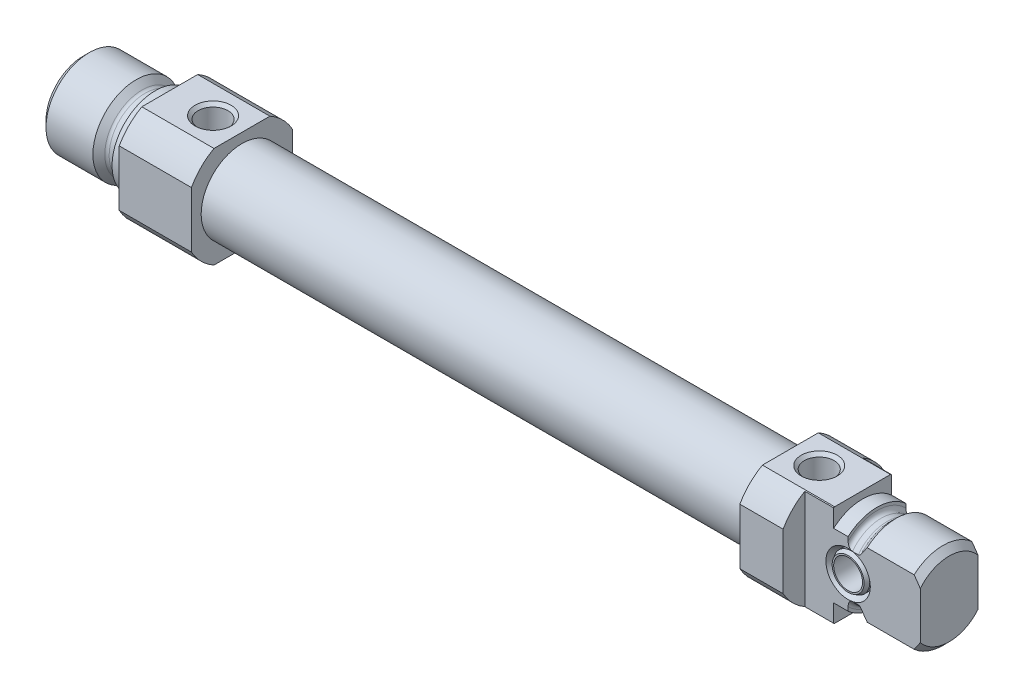
SolidWorks part; units mm, degrees
ref_plane "Front Plane" through (0, 0, 0) normal (0, 0, 1) x (1, 0, 0)
ref_plane "Top Plane" through (0, 0, 0) normal (0, 1, 0) x (1, 0, 0)
ref_plane "Right Plane" through (0, 0, 0) normal (1, 0, 0) x (0, 0, -1)
sketch "Sketch1" plane through (0, 0, 0) normal (0, 0, 1) x (1, 0, 0)
  line L0 (0, 0) -> (0, 5.15)
  line L1 (0, 5.15) -> (0.85, 6)
  line L2 (0.85, 6) -> (7.35, 6)
  line L3 (7.35, 6) -> (8.1743, 5.1757)
  line L4 (8.5985, 5) -> (9.4, 5)
  line L5 (10, 5.6) -> (10, 6)
  line L6 (10, 6) -> (12, 6)
  line L7 (12, 6) -> (12, 0)
  line L8 (12, 0) -> (0, 0)
  line L9 (12, 0) -> (0, 0) construction
  arc A0 (8.1743, 5.1757) -> (8.5985, 5) centre (8.5985, 5.6) ccw
  arc A1 (9.4, 5) -> (10, 5.6) centre (9.4, 5.6) ccw
revolve "Revolve1" add sketch "Sketch1" angle 360 about L9 reverse direction yes
cosmetic thread "Cosmetic Thread1" parameters "D1"=7.267, "D2"=10.466
ref_plane "Plane1" through (3, 0, 0) normal (1, 0, 0) x (0, 0, -1)
ref_plane "Plane2" through (8, 0, 0) normal (1, 0, 0) x (0, 0, -1)
ref_plane "Plane3" through (0, -8, 0) normal (0, 1, 0) x (1, 0, 0)
ref_plane "Plane4" through (0, 0, 0) normal (0, 1, 0) x (1, 0, 0)
ref_plane "Plane5" through (0, 0, 0) normal (0, 1, 0) x (1, 0, 0)
ref_plane "Plane6" through (0, 0, 0) normal (0, 1, 0) x (1, 0, 0)
ref_plane "Plane7" through (12, 0, 0) normal (1, 0, 0) x (0, 0, -1)
ref_plane "Plane8" through (12, 0, 0) normal (1, 0, 0) x (0, 0, -1)
ref_plane "Plane9" through (20, 0, 0) normal (1, 0, 0) x (0, 0, -1)
ref_plane "Plane10" through (12, 0, 0) normal (1, 0, 0) x (0, 0, -1)
ref_plane "Plane11" through (12, 0, 0) normal (1, 0, 0) x (0, 0, -1)
sketch "Sketch2" plane through (12, 0, 0) normal (1, 0, 0) x (0, 0, -1)
  line L0 (-3.873, -7) -> (3.873, -7)
  line L1 (7, -3.873) -> (7, 3.873)
  line L2 (3.873, 7) -> (-3.873, 7)
  line L3 (-7, 3.873) -> (-7, -3.873)
  arc A0 (-7, -3.873) -> (-3.873, -7) centre (0, 0) ccw
  arc A1 (3.873, -7) -> (7, -3.873) centre (0, 0) ccw
  arc A2 (7, 3.873) -> (3.873, 7) centre (0, 0) ccw
  arc A3 (-3.873, 7) -> (-7, 3.873) centre (0, 0) ccw
extrude "Boss-Extrude1" add sketch "Sketch2" along normal blind 10
ref_plane "Plane12" through (12, 0, 0) normal (1, 0, 0) x (0, 0, -1)
ref_plane "Plane13" through (0, 0, 0) normal (0, 0, 1) x (1, 0, 0)
ref_plane "Plane14" through (0, 0, 0) normal (0, 0, 1) x (1, 0, 0)
ref_plane "Plane15" through (0, 0, 0) normal (0, 1, 0) x (1, 0, 0)
ref_plane "Plane16" through (0, 0, 0) normal (0, 1, 0) x (1, 0, 0)
ref_plane "Plane17" through (0, 0, -6.6) normal (0, 0, 1) x (1, 0, 0)
ref_plane "Plane18" through (0, 0, 0) normal (0, 1, 0) x (1, 0, 0)
ref_plane "Plane19" through (0, 0, 0) normal (0, 1, 0) x (1, 0, 0)
ref_plane "Plane20" through (0, 1.1287, -0.199) normal (0, 0.9848, -0.1736) x (1, 0, 0)
ref_plane "Plane21" through (0, -0.3485, 0.0615) normal (0, 0.9848, -0.1736) x (1, 0, 0)
sketch "Sketch3" plane through (0, 0, 0) normal (0, 0, 1) x (1, 0, 0)
  line L0 (22, 0) -> (22, 5.65)
  line L1 (22, 5.65) -> (98, 5.65)
  line L2 (98, 5.65) -> (98, 0)
  line L3 (98, 0) -> (22, 0)
  line L4 (98, 0) -> (22, 0) construction
revolve "Revolve2" add sketch "Sketch3" angle 360 about L4 reverse direction yes
ref_plane "Plane22" through (98, 0, 0) normal (1, 0, 0) x (0, 0, -1)
sketch "Sketch4" plane through (98, 0, 0) normal (1, 0, 0) x (0, 0, -1)
  line L0 (-7, -7) -> (7, -7)
  line L1 (7, -7) -> (7, 7)
  line L2 (7, 7) -> (-7, 7)
  line L3 (-7, 7) -> (-7, -7)
extrude "Boss-Extrude2" add sketch "Sketch4" along normal blind 10
sketch "Sketch5" plane through (0, 0, 0) normal (0, 0, 1) x (1, 0, 0)
  line L0 (98, 18) -> (98, 8)
  line L1 (98, 8) -> (108, 8)
  line L2 (108, 8) -> (108, 18)
  line L3 (108, 18) -> (98, 18)
  line L4 (108, 0) -> (98, 0) construction
revolve "Cut-Revolve1" cut sketch "Sketch5" angle 360 about L4 reverse direction yes
ref_plane "Plane23" through (98, 0, 0) normal (1, 0, 0) x (0, 0, -1)
ref_plane "Plane24" through (108, 0, 0) normal (1, 0, 0) x (0, 0, -1)
ref_plane "Plane25" through (0, 0, 6.6) normal (0, 0, 1) x (1, 0, 0)
ref_plane "Plane26" through (0, 0, 0) normal (0, 1, 0) x (1, 0, 0)
ref_plane "Plane27" through (0, 0, 0) normal (0, 1, 0) x (1, 0, 0)
ref_plane "Plane28" through (0, 1.1287, 0.199) normal (0, 0.9848, 0.1736) x (1, 0, 0)
ref_plane "Plane29" through (0, -0.3485, -0.0615) normal (0, 0.9848, 0.1736) x (1, 0, 0)
ref_plane "Plane30" through (137, 0, 0) normal (1, 0, 0) x (0, 0, -1)
sketch "Sketch6" plane through (0, 0, 0) normal (0, 0, 1) x (1, 0, 0)
  line L0 (108, 0) -> (108, 6)
  line L1 (108, 6) -> (110, 6)
  line L2 (110, 6) -> (110, 5.6)
  line L3 (110.6, 5) -> (111.4015, 5)
  line L4 (111.8257, 5.1757) -> (112.65, 6)
  line L5 (112.65, 6) -> (119.15, 6)
  line L6 (119.15, 6) -> (120, 5.15)
  line L7 (120, 5.15) -> (120, 0)
  line L8 (120, 0) -> (108, 0)
  line L9 (120, 0) -> (108, 0) construction
  arc A0 (110, 5.6) -> (110.6, 5) centre (110.6, 5.6) ccw
  arc A1 (111.4015, 5) -> (111.8257, 5.1757) centre (111.4015, 5.6) ccw
revolve "Revolve3" add sketch "Sketch6" angle 360 about L9 reverse direction yes
cosmetic thread "Cosmetic Thread2" parameters "D1"=7.267, "D2"=10.466
ref_plane "Plane31" through (129, 0, 0) normal (1, 0, 0) x (0, 0, -1)
ref_plane "Plane32" through (137, 0, 0) normal (1, 0, 0) x (0, 0, -1)
ref_plane "Plane33" through (137, 0, 0) normal (1, 0, 0) x (0, 0, -1)
sketch "Sketch7" plane through (0, 0, 0) normal (0, 1, 0) x (1, 0, 0)
  line L0 (104, 12) -> (104, 4)
  line L1 (104, 4) -> (120, 4)
  line L2 (120, 4) -> (120, -4)
  line L3 (120, -4) -> (104, -4)
  line L4 (104, -4) -> (104, -12)
  line L5 (104, -12) -> (128, -12)
  line L6 (128, -12) -> (128, 12)
  line L7 (128, 12) -> (104, 12)
extrude "Cut-Extrude1" cut sketch "Sketch7" along normal blind 8 and the other way blind 8
ref_plane "Plane34" through (110, 0, 0) normal (1, 0, 0) x (0, 0, -1)
sketch "Sketch8" plane through (110, 0, 0) normal (1, 0, 0) x (0, 0, -1)
  line L0 (-4.2, 0) -> (-4.2, 3.1928)
  line L1 (-4.2, 3.1928) -> (-3, 2.5)
  line L2 (-3, 2.5) -> (-3.5, 2.5)
  line L3 (-3.5, 2.5) -> (-4, 2.2113)
  line L4 (-4, 2.2113) -> (-4, 2)
  line L5 (-4, 2) -> (4, 2)
  line L6 (4, 2) -> (4, 2.2113)
  line L7 (4, 2.2113) -> (3.5, 2.5)
  line L8 (3.5, 2.5) -> (3, 2.5)
  line L9 (3, 2.5) -> (4.2, 3.1928)
  line L10 (4.2, 3.1928) -> (4.2, 0)
  line L11 (4.2, 0) -> (-4.2, 0)
  line L12 (4, 0) -> (-4.2, 0) construction
revolve "Cut-Revolve2" cut sketch "Sketch8" angle 360 about L12 reverse direction yes
hole_wizard "Hole1" positions "Sketch10" profile "Sketch9" legacy
sketch "Sketch10" plane through (0, 7, 0) normal (0, 1, 0) x (1, 0, 0)
  point P0 (18, 0)
sketch "Sketch9" plane through (18, 7, 0) normal (1, 0, 0) x (0, 0, 1)
  line L0 (0, 0) -> (0, 7)
  line L1 (0, 7) -> (2.067, 7)
  line L2 (2.067, 7) -> (2.067, 0.433)
  line L3 (2.067, 0.433) -> (2.5, 0)
  line L4 (2.5, 0) -> (0, 0)
  line L5 (0, -6.4453) -> (0, 115.525) construction
  line L6 (-2.067, 0.433) -> (-2.5, 0) construction
  dimension "Diameter" = 4.134
  dimension "Depth" = 7
  dimension "C-Sink Angle" = 90
  dimension "C-Sink Diameter" = 5
cosmetic thread "Cosmetic Thread3" parameters "D1"=6, "D2"=5
hole_wizard "Hole2" positions "Sketch12" profile "Sketch11" legacy
sketch "Sketch12" plane through (0, 7, 0) normal (0, 1, 0) x (1, 0, 0)
  point P0 (102, 0)
sketch "Sketch11" plane through (102, 7, 0) normal (1, 0, 0) x (0, 0, 1)
  line L0 (0, 0) -> (0, 9.1934)
  line L1 (0, 9.1934) -> (2.067, 8)
  line L2 (2.067, 8) -> (2.067, 0.433)
  line L3 (2.067, 0.433) -> (2.5, 0)
  line L4 (2.5, 0) -> (0, 0)
  line L5 (0, -14.3089) -> (0, 102.4216) construction
  line L6 (0, 9.1934) -> (-2.067, 8) construction
  line L7 (-2.067, 0.433) -> (-2.5, 0) construction
  dimension "Diameter" = 4.134
  dimension "Depth" = 8
  dimension "C-Sink Diameter" = 5
  dimension "C-Sink Angle" = 90
  dimension "Drill Angle" = 120
cosmetic thread "Cosmetic Thread4" parameters "D1"=6, "D2"=5
sketch "Sketch13" plane through (0, 0, 0) normal (0, 0, 1) x (1, 0, 0)
  line L0 (-4, 0) -> (-4, 2)
  line L1 (-4, 2) -> (31.5, 2)
  line L2 (31.5, 2) -> (31.5, 5)
  line L3 (31.5, 5) -> (84, 5)
  line L4 (84, 5) -> (84, 0)
  line L5 (84, 0) -> (-4, 0)
  line L6 (84, 0) -> (-4, 0) construction
revolve "Cut-Revolve3" cut sketch "Sketch13" angle 360 about L6 reverse direction yes
ref_plane "Plane35" through (-4, 0, 0) normal (1, 0, 0) x (0, 0, -1)
ref_plane "Plane36" through (0, 7, 0) normal (0, 1, 0) x (1, 0, 0)
ref_plane "Plane37" through (6, 0, 0) normal (1, 0, 0) x (0, 0, -1)
ref_plane "Plane38" through (0, 0, 0) normal (1, 0, 0) x (0, 0, -1)
ref_plane "Plane39" through (12, 0, 0) normal (1, 0, 0) x (0, 0, -1)
ref_plane "Plane40" through (108, 0, 0) normal (1, 0, 0) x (0, 0, -1)
ref_plane "Plane41" through (12, 0, 0) normal (1, 0, 0) x (0, 0, -1)
ref_plane "Plane42" through (0, 7, 0) normal (0, 1, 0) x (1, 0, 0)
ref_plane "Plane43" through (31.5, 0, 0) normal (1, 0, 0) x (0, 0, -1)
ref_plane "Plane44" through (88.5, 0, 0) normal (1, 0, 0) x (0, 0, -1)
ref_plane "Plane45" through (0, 0, 0) normal (0, 0, 1) x (1, 0, 0)
ref_plane "Plane46" through (12, 0, 0) normal (1, 0, 0) x (0, 0, -1)
ref_plane "Plane47" through (0, 7, 0) normal (0, 1, 0) x (1, 0, 0)
ref_plane "Plane48" through (3, 0, 0) normal (1, 0, 0) x (0, 0, -1)
ref_plane "Plane49" through (0, 7, 0) normal (0, 1, 0) x (1, 0, 0)
ref_plane "FDT_FRONT XY" through (12, 0, 0) normal (1, 0, 0) x (0, 0, -1)
ref_plane "FDT_FRONT XZ" through (0, 0, 0) normal (0, -1, 0) x (-1, 0, 0)
ref_plane "FDT_FRONT YZ" through (0, 0, 0) normal (0, 0, -1) x (-1, 0, 0)
ref_axis "FDT_FRONT X" through (12, 0, 80.9) along (0, 0, -1)
ref_axis "FDT_FRONT Y" through (12, -50, 0) along (0, 1, 0)
ref_axis "FDT_FRONT Z" through (80.9, 0, 0) along (-1, 0, 0)
sketch3d "FDT_FRONT"
  point P0 (12, 0, 0)
ref_plane "FDT_QSFRONT XY" through (0, 7, 0) normal (0, 1, 0) x (1, 0, 0)
ref_plane "FDT_QSFRONT XZ" through (18, 0, 0) normal (-1, 0, 0) x (0, 0, 1)
ref_plane "FDT_QSFRONT YZ" through (0, 0, 0) normal (0, 0, 1) x (1, 0, 0)
ref_axis "FDT_QSFRONT X" through (18, 7, -50) along (0, 0, 1)
ref_axis "FDT_QSFRONT Y" through (-80.9, 7, 0) along (1, 0, 0)
ref_axis "FDT_QSFRONT Z" through (18, 50, 0) along (0, -1, 0)
sketch3d "FDT_QSFRONT"
  point P0 (18, 7, 0)
ref_plane "FDT_QSREAR XY" through (0, 7, 0) normal (0, 1, 0) x (1, 0, 0)
ref_plane "FDT_QSREAR XZ" through (102, 0, 0) normal (-1, 0, 0) x (0, 0, 1)
ref_plane "FDT_QSREAR YZ" through (0, 0, 0) normal (0, 0, 1) x (1, 0, 0)
ref_axis "FDT_QSREAR X" through (102, 7, -50) along (0, 0, 1)
ref_axis "FDT_QSREAR Y" through (-80.9, 7, 0) along (1, 0, 0)
ref_axis "FDT_QSREAR Z" through (102, 50, 0) along (0, -1, 0)
sketch3d "FDT_QSREAR"
  point P0 (102, 7, 0)
ref_plane "FDT_REAR XY" through (108, 0, 0) normal (-1, 0, 0) x (0, 0, 1)
ref_plane "FDT_REAR XZ" through (0, 0, 0) normal (0, 1, 0) x (1, 0, 0)
ref_plane "FDT_REAR YZ" through (0, 0, 0) normal (0, 0, -1) x (-1, 0, 0)
ref_axis "FDT_REAR X" through (108, 0, 80.9) along (0, 0, -1)
ref_axis "FDT_REAR Y" through (108, 50, 0) along (0, -1, 0)
ref_axis "FDT_REAR Z" through (-80.9, 0, 0) along (1, 0, 0)
sketch3d "FDT_REAR"
  point P0 (108, 0, 0)
ref_plane "FDT_SMBR1 XY" through (31.5, 0, 0) normal (-1, 0, 0) x (0, 0, 1)
ref_plane "FDT_SMBR1 XZ" through (0, 0, 0) normal (0, -1, 0) x (-1, 0, 0)
ref_plane "FDT_SMBR1 YZ" through (0, 0, 0) normal (0, 0, 1) x (1, 0, 0)
ref_axis "FDT_SMBR1 X" through (31.5, 0, -80.9) along (0, 0, 1)
ref_axis "FDT_SMBR1 Y" through (31.5, -50, 0) along (0, 1, 0)
ref_axis "FDT_SMBR1 Z" through (-80.9, 0, 0) along (1, 0, 0)
sketch3d "FDT_SMBR1"
  point P0 (31.5, 0, 0)
ref_plane "FDT_SMBR2 XY" through (88.5, 0, 0) normal (-1, 0, 0) x (0, 0, 1)
ref_plane "FDT_SMBR2 XZ" through (0, 0, 0) normal (0, -1, 0) x (-1, 0, 0)
ref_plane "FDT_SMBR2 YZ" through (0, 0, 0) normal (0, 0, 1) x (1, 0, 0)
ref_axis "FDT_SMBR2 X" through (88.5, 0, -80.9) along (0, 0, 1)
ref_axis "FDT_SMBR2 Y" through (88.5, -50, 0) along (0, 1, 0)
ref_axis "FDT_SMBR2 Z" through (-80.9, 0, 0) along (1, 0, 0)
sketch3d "FDT_SMBR2"
  point P0 (88.5, 0, 0)
ref_plane "FDT_SWIVELAXIS XY" through (0, 0, 0) normal (0, 0, 1) x (1, 0, 0)
ref_plane "FDT_SWIVELAXIS XZ" through (0, 0, 0) normal (0, -1, 0) x (-1, 0, 0)
ref_plane "FDT_SWIVELAXIS YZ" through (110, 0, 0) normal (1, 0, 0) x (0, 0, -1)
ref_axis "FDT_SWIVELAXIS X" through (-80.9, 0, 0) along (1, 0, 0)
ref_axis "FDT_SWIVELAXIS Y" through (110, -50, 0) along (0, 1, 0)
ref_axis "FDT_SWIVELAXIS Z" through (110, 0, 80.9) along (0, 0, -1)
sketch3d "FDT_SWIVELAXIS"
  point P0 (110, 0, 0)
ref_plane "NUT XY" through (6, 0, 0) normal (1, 0, 0) x (0, 0, -1)
ref_plane "NUT XZ" through (0, 0, 0) normal (0, -1, 0) x (-1, 0, 0)
ref_plane "NUT YZ" through (0, 0, 0) normal (0, 0, -1) x (-1, 0, 0)
ref_axis "NUT X" through (6, 0, 80.9) along (0, 0, -1)
ref_axis "NUT Y" through (6, -50, 0) along (0, 1, 0)
ref_axis "NUT Z" through (80.9, 0, 0) along (-1, 0, 0)
sketch3d "NUT"
  point P0 (6, 0, 0)
ref_plane "ZR XY" through (0, 0, 0) normal (-1, 0, 0) x (0, 0, 1)
ref_plane "ZR XZ" through (0, 0, 0) normal (0, 1, 0) x (1, 0, 0)
ref_plane "ZR YZ" through (0, 0, 0) normal (0, 0, -1) x (-1, 0, 0)
ref_axis "ZR X" through (0, 0, 80.9) along (0, 0, -1)
ref_axis "ZR Y" through (0, 50, 0) along (0, -1, 0)
ref_axis "ZR Z" through (-80.9, 0, 0) along (1, 0, 0)
sketch3d "ZR"
  point P0 (0, 0, 0)
ref_plane "ZYL XY" through (12, 0, 0) normal (1, 0, 0) x (0, 0, -1)
ref_plane "ZYL XZ" through (0, 0, 0) normal (0, -1, 0) x (-1, 0, 0)
ref_plane "ZYL YZ" through (0, 0, 0) normal (0, 0, -1) x (-1, 0, 0)
ref_axis "ZYL X" through (12, 0, 80.9) along (0, 0, -1)
ref_axis "ZYL Y" through (12, -50, 0) along (0, 1, 0)
ref_axis "ZYL Z" through (80.9, 0, 0) along (-1, 0, 0)
sketch3d "ZYL"
  point P0 (12, 0, 0)
